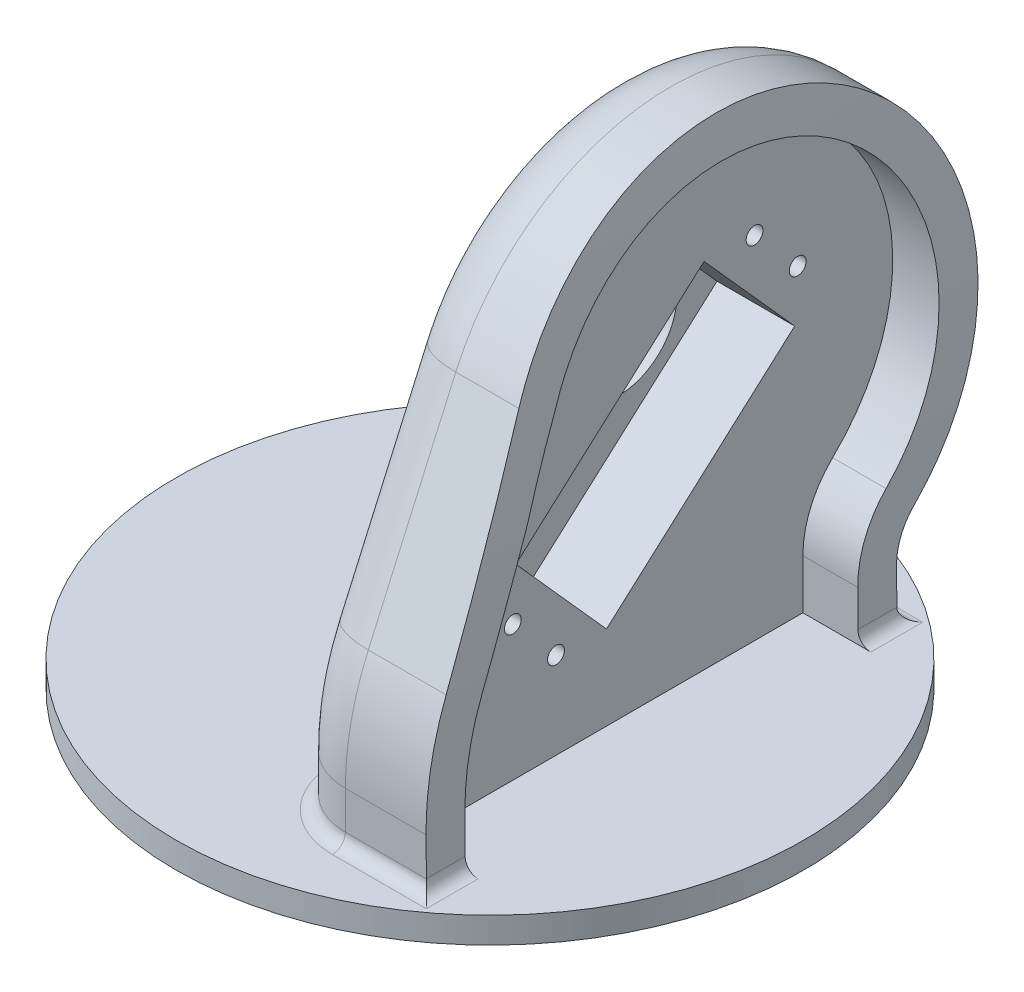
SolidWorks part; units mm, degrees
ref_plane "Front Plane" through (0, 0, 0) normal (0, 0, 1) x (1, 0, 0)
ref_plane "Top Plane" through (0, 0, 0) normal (0, 1, 0) x (1, 0, 0)
ref_plane "Right Plane" through (0, 0, 0) normal (1, 0, 0) x (0, 0, -1)
sketch "Sketch2" plane through (0, 0, 0) normal (0, 1, 0) x (1, 0, 0)
  line L0 (0, -7.25) -> (0, 7.25) construction
  circle A0 centre (0, 0) radius 48.5
  circle A1 centre (0, 7.25) radius 1.5
  circle A2 centre (0, -7.25) radius 1.5
  point P6 (0, 0)
  dimension "D1" = 97
  dimension "D3" = 3
  dimension "D2" = 14.5
extrude "Boss-Extrude1" add sketch "Sketch2" along normal blind 4
sketch "Sketch3" plane through (0, 0, 0) normal (0, -1, 0) x (1, 0, 0)
  circle A0 centre (0, 0) radius 3.75
  dimension "D1" = 7.5
extrude "Cut-Extrude1" cut sketch "Sketch3" against normal blind 1.5
sketch "Sketch5" plane through (0, 0, 0) normal (1, 0, 0) x (0, 0, -1)
  line L0 (30.34, 4) -> (-30.34, 4)
  line L1 (48.5, 4) -> (-48.5, 4) construction
  line L2 (30.34, 4) -> (30.34, 11.64)
  line L3 (-30.34, 4) -> (-30.34, 11.86)
  line L4 (-27.3065, 26.1616) -> (-13.7924, 56.5853)
  arc A0 (30.34, 11.64) -> (34.9356, 22.445) centre (45.34, 11.64) cw
  arc A1 (34.9356, 22.445) -> (-13.7924, 56.5853) centre (13.91, 44.28) ccw
  arc A2 (-30.34, 11.86) -> (-27.3065, 26.1616) centre (4.89, 11.86) cw
  circle A3 centre (13.91, 44.28) radius 9
  point P5 (0, 4)
  dimension "D3" = 15
  dimension "D5" = 35.23
  dimension "D6" = 18
  dimension "D1" = 60.68
  dimension "D2" = 7.64
  dimension "D4" = 7.86
  dimension "D7" = 13.91
  dimension "D8" = 40.28
sketch "Sketch6" plane through (0, 0, 0) normal (1, 0, 0) x (0, 0, -1)
extrude "Boss-Extrude3" add sketch "Sketch5" along normal blind 14 from offset 4
sketch "Sketch9" plane through (0, 0, 0) normal (1, 0, 0) x (0, 0, -1)
  line L0 (0, 17) -> (29.0759, 42.9921)
  line L1 (0, 17) -> (-13.9958, 32.6563)
  line L2 (29.0759, 42.9921) -> (15.0802, 58.6484)
  line L3 (-13.9958, 32.6563) -> (15.0802, 58.6484)
  line L4 (48.5, 4) -> (-48.5, 4) construction
  line L5 (0.5422, 45.6523) -> (14.538, 29.9961) construction
  line L6 (7.5401, 37.8242) -> (26.2084, 54.5125) construction
  line L7 (29.5407, 50.7848) -> (22.8761, 58.2402) construction
  circle A0 centre (29.5407, 50.7848) radius 1.3
  circle A1 centre (22.8761, 58.2402) radius 1.3
  circle A2 centre (-7.7959, 17.4082) radius 1.3
  circle A3 centre (-14.4605, 24.8636) radius 1.3
  point P13 (26.2084, 54.5125)
  dimension "D4" = 5.5401
  dimension "D6" = 2.6
  dimension "D1" = 39
  dimension "D2" = 21
  dimension "D3" = 13
  dimension "D5" = 10
sketch "Sketch10" plane through (0, 0, 0) normal (1, 0, 0) x (0, 0, -1)
extrude "Cut-Extrude2" cut sketch "Sketch9" along normal through all from offset 6
sketch "Sketch11" plane through (18, 0, 0) normal (1, 0, 0) x (0, 0, -1)
  line L0 (33.34, 4) -> (33.34, 11.64) construction
  line L1 (-16.534, 57.8032) -> (-30.0482, 27.3795) construction
  line L2 (-33.34, 11.86) -> (-33.34, 4) construction
  line L3 (-19.2757, 59.021) -> (-32.7899, 28.5973)
  line L4 (-30.34, 11.86) -> (-30.34, 4)
  line L5 (-30.34, 4) -> (30.34, 4)
  line L6 (30.34, 4) -> (30.34, 11.64)
  line L7 (-13.7924, 56.5853) -> (-27.3065, 26.1616)
  line L8 (-30.34, 11.86) -> (-30.34, 4) construction
  line L9 (-30.34, 4) -> (30.34, 4)
  line L10 (30.34, 4) -> (30.34, 11.64)
  line L11 (-13.7924, 56.5853) -> (-27.3065, 26.1616) construction
  line L12 (-36.34, 11.86) -> (-36.34, 4)
  line L13 (36.34, 4) -> (36.34, 11.64)
  line L14 (-36.34, 4) -> (-27.34, 4)
  line L15 (30.34, 4) -> (36.34, 4)
  arc A0 (37.0165, 20.284) -> (33.34, 11.64) centre (45.34, 11.64) ccw construction
  arc A1 (37.0165, 20.284) -> (-16.534, 57.8032) centre (13.91, 44.28) ccw construction
  arc A2 (-30.0482, 27.3795) -> (-33.34, 11.86) centre (4.89, 11.86) ccw construction
  arc A3 (34.9356, 22.445) -> (30.34, 11.64) centre (45.34, 11.64) ccw
  arc A4 (34.9356, 22.445) -> (-13.7924, 56.5853) centre (13.91, 44.28) ccw
  arc A5 (-27.3065, 26.1616) -> (-30.34, 11.86) centre (4.89, 11.86) ccw
  arc A6 (34.9356, 22.445) -> (30.34, 11.64) centre (45.34, 11.64) ccw
  arc A7 (34.9356, 22.445) -> (-13.7924, 56.5853) centre (13.91, 44.28) ccw
  arc A8 (-27.3065, 26.1616) -> (-30.34, 11.86) centre (4.89, 11.86) ccw construction
  arc A9 (-32.7899, 28.5973) -> (-36.34, 11.86) centre (4.89, 11.86) ccw
  arc A10 (39.0973, 18.123) -> (36.34, 11.64) centre (45.34, 11.64) ccw
  arc A11 (39.0973, 18.123) -> (-19.2757, 59.021) centre (13.91, 44.28) ccw
  arc A12 (-13.7924, 56.5853) -> (-27.34, 4) centre (96.7775, 0.0613) ccw
  dimension "D5" = 3
  dimension "D1" = 0
  dimension "D2" = 3
  dimension "D3" = 3
  dimension "D4" = 3
sketch "Sketch12" plane through (0, 0, 0) normal (1, 0, 0) x (0, 0, -1)
extrude "Boss-Extrude6" add sketch "Sketch11" along normal blind 9 and the other way up to surface (14 mm away) contours A12 L7 L6 L5 L15 L13 A10 A11 L3 A9 L12 L14 region at (18, 73.0728, -34.0832) other way up to face at (4, 23.8443, -1.8168)
sketch "Sketch14" plane through (0, 0, 0) normal (0, 0, 1) x (1, 0, 0)
  line L0 (27, 80.5924) -> (21, 80.5924)
  line L1 (27, 80.5924) -> (4, 80.5924) construction
  line L2 (4, 4) -> (27, 4) construction
  line L3 (27, 80.5924) -> (27, 4)
  line L4 (27, 4) -> (26.5, 4)
  arc A0 (21, 80.5924) -> (26.5, 4) centre (-473.4933, 6.5898) cw
  dimension "D3" = 500
  dimension "D1" = 6
  dimension "D2" = 0.5
extrude "Cut-Extrude3" cut sketch "Sketch14" against normal through all both and the other way through all
fillet "Fillet2" radius 10 6 edges at (4, 7.82, -36.34) (4, 15.1625, -37.058) (4, 7.93, 36.34) (4, 20.4149, 35.4427) (4, 43.8092, 26.0328) (4, 74.0194, -34.7464)
fillet "Fillet3" radius 2 5 edges at (20.25, 4, 36.34) (6.9289, 4, 33.4111) (20.25, 4, -36.34) (6.9289, 4, -33.4111) (4, 4, 0)
fillet "Fillet4" radius 2 2 edges at (26.5, 4, -34.34) (26.5, 4, 34.34)
